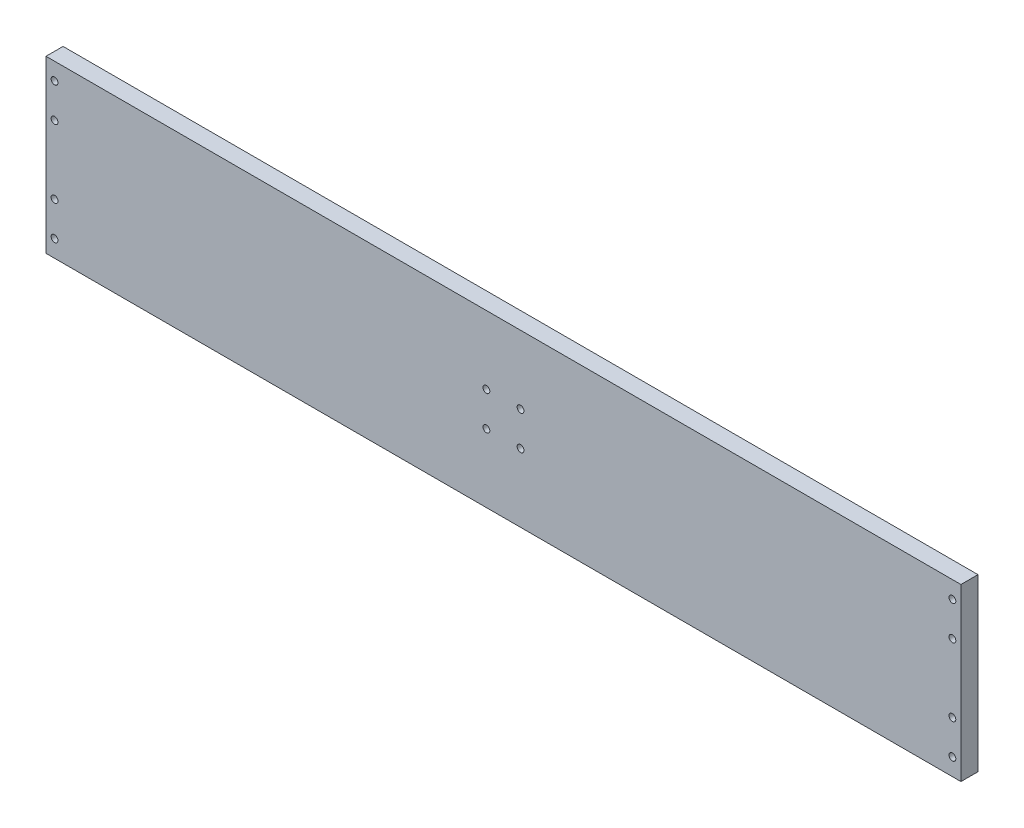
SolidWorks part; units mm, degrees
ref_plane "Piano frontale" through (0, 0, 0) normal (0, 0, 1) x (1, 0, 0)
ref_plane "Piano superiore" through (0, 0, 0) normal (0, 1, 0) x (1, 0, 0)
ref_plane "Piano destro" through (0, 0, 0) normal (1, 0, 0) x (0, 0, -1)
sketch "Schizzo1" plane through (0, 0, 0) normal (0, 0, 1) x (1, 0, 0)
  line L0 (5, 100) -> (5, 0) construction
  line L1 (0, 0) -> (536, 0)
  line L2 (0, 0) -> (0, 100)
  line L3 (0, 100) -> (536, 100)
  line L4 (536, 0) -> (536, 100)
  line L5 (0, 50) -> (10.4526, 50) construction
  line L6 (268, 100) -> (268, 0) construction
  line L7 (536, 50) -> (525.5474, 50) construction
  line L8 (531, 100) -> (531, 0) construction
  circle A0 centre (5, 90) radius 2
  circle A1 centre (5, 70) radius 2
  circle A2 centre (5, 30) radius 2
  circle A3 centre (531, 10) radius 2
  circle A4 centre (531, 30) radius 2
  circle A5 centre (531, 70) radius 2
  circle A6 centre (5, 10) radius 2
  circle A7 centre (531, 90) radius 2
  dimension "D4" = 4
  dimension "D5" = 5
  dimension "D1" = 100
  dimension "D2" = 536
  dimension "D3" = 40
  dimension "D6" = 20
extrude "Estrusione-Estrusione1" add sketch "Schizzo1" against normal blind 10
sketch "Schizzo2" plane through (0, 0, 0) normal (0, 0, 1) x (1, 0, 0)
  line L0 (268, 100) -> (268, 0) construction
  line L1 (536, 100) -> (0, 100) construction
  line L2 (0, 50) -> (536, 50) construction
  line L3 (0, 0) -> (536, 0) construction
  line L4 (285, 50) -> (265, 50) construction
  line L9 (0, 100) -> (0, 0) construction
  line L10 (536, 0) -> (536, 100) construction
  circle A0 centre (258, 60) radius 2
  circle A1 centre (278, 60) radius 2
  circle A4 centre (278, 40) radius 2
  circle A5 centre (258, 40) radius 2
  dimension "D3" = 4
  dimension "D1" = 10
  dimension "D2" = 10
  dimension "D4" = 10
extrude "Taglio-Estrusione1" cut sketch "Schizzo2" against normal through all
